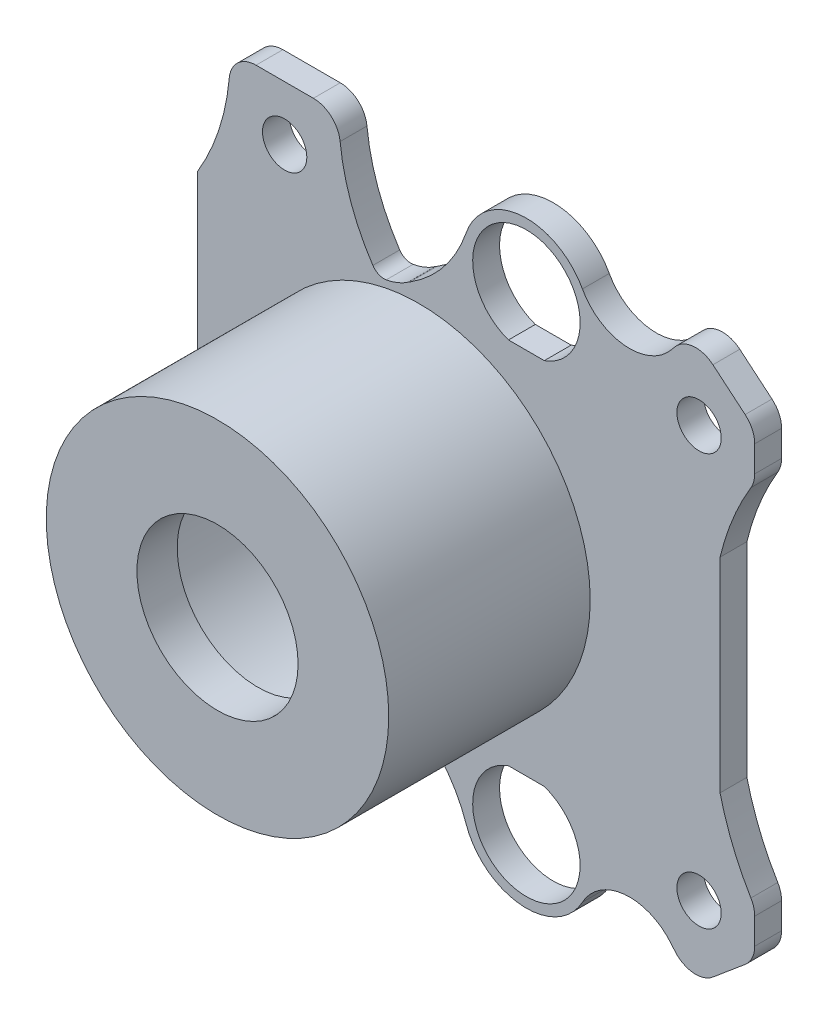
SolidWorks part; units mm, degrees
material "PETG"
ref_plane "Спереди" through (0, 0, 0) normal (0, 0, 1) x (1, 0, 0)
ref_plane "Сверху" through (0, 0, 0) normal (0, 1, 0) x (1, 0, 0)
ref_plane "Справа" through (0, 0, 0) normal (1, 0, 0) x (0, 0, -1)
sketch "Эскиз1" plane through (0, 0, 0) normal (0, 0, 1) x (1, 0, 0)
  line L0 (25, -14.2588) -> (25, -16.1977) construction
  line L1 (21.8887, -19.7411) -> (24.2856, -17.7298) construction
  line L2 (18.7497, -19.1116) -> (19.071, -19.4946) construction
  line L3 (-12.13, -22.05) -> (-7.8593, -22.05) construction
  line L4 (25, 16.1977) -> (25, 14.2588) construction
  line L5 (24.2856, 17.7298) -> (21.8887, 19.7411) construction
  line L6 (19.071, 19.4946) -> (18.7497, 19.1116) construction
  line L7 (-7.8593, 22.05) -> (-12.13, 22.05) construction
  line L8 (25, -14.2588) -> (25, -16.1977)
  line L9 (21.8887, -19.7411) -> (24.2856, -17.7298)
  line L10 (18.7497, -19.1116) -> (19.071, -19.4946)
  line L11 (-12.13, -22.05) -> (-7.8593, -22.05)
  line L12 (25, 16.1977) -> (25, 14.2588)
  line L13 (24.2856, 17.7298) -> (21.8887, 19.7411)
  line L14 (19.071, 19.4946) -> (18.7497, 19.1116)
  line L15 (-7.8593, 22.05) -> (-12.13, 22.05)
  line L16 (-16.5, -13) -> (-16.5, 13) construction
  line L17 (-16.5, -13) -> (-16.5, 13)
  line L18 (-3.4328, 13.4865) -> (-3.4328, 8.5896)
  line L19 (-3.4328, -13.4865) -> (-3.4328, -8.5896)
  line L20 (12, -17.5) -> (12, -13.7292) construction
  line L21 (20.1132, -7.6) -> (22.4198, -7.6) construction
  line L22 (22.4198, 7.6) -> (20.1132, 7.6) construction
  line L23 (12, 13.7292) -> (12, 17.5) construction
  line L24 (12, -17.5) -> (12, -13.7292)
  line L25 (20.1132, -7.6) -> (22.4198, -7.6)
  line L26 (22.4198, 7.6) -> (20.1132, 7.6)
  line L27 (12, 13.7292) -> (12, 17.5)
  line L30 (12, 17.5) -> (13.0411, 18.6816)
  line L31 (12, -17.5) -> (13.0411, -18.6816)
  circle A0 centre (20.8558, -15.3209) radius 2.05 construction
  circle A1 centre (-10, -18) radius 2.05 construction
  circle A2 centre (20.8558, 15.3209) radius 2.05 construction
  circle A3 centre (-10, 18) radius 2.05 construction
  circle A4 centre (20.8558, -15.3209) radius 2.05
  circle A5 centre (-10, -18) radius 2.05
  circle A6 centre (20.8558, 15.3209) radius 2.05
  circle A7 centre (-10, 18) radius 2.05
  arc A8 (22.4198, -7.6) -> (24.7157, -13.2309) centre (41.8722, -2.9522) ccw construction
  arc A9 (25, -14.2588) -> (24.7157, -13.2309) centre (23, -14.2588) ccw construction
  arc A10 (24.2856, -17.7298) -> (25, -16.1977) centre (23, -16.1977) ccw construction
  arc A11 (19.071, -19.4946) -> (21.8887, -19.7411) centre (20.6031, -18.209) ccw construction
  arc A12 (18.7497, -19.1116) -> (12.1721, -19.7707) centre (15.6855, -21.6828) ccw construction
  arc A13 (-3.4328, -13.4865) -> (-5.87, -20.2563) centre (9.05, -21.8039) ccw construction
  arc A14 (-7.8593, -22.05) -> (-5.87, -20.2563) centre (-7.8593, -20.05) ccw construction
  arc A15 (-14.1216, -20.2334) -> (-12.13, -22.05) centre (-12.13, -20.05) ccw construction
  arc A16 (-14.1216, -20.2334) -> (-16.5, -13) centre (-31.05, -21.7919) ccw construction
  arc A17 (24.7157, 13.2309) -> (22.4198, 7.6) centre (41.8722, 2.9522) ccw construction
  arc A18 (24.7157, 13.2309) -> (25, 14.2588) centre (23, 14.2588) ccw construction
  arc A19 (25, 16.1977) -> (24.2856, 17.7298) centre (23, 16.1977) ccw construction
  arc A20 (21.8887, 19.7411) -> (19.071, 19.4946) centre (20.6031, 18.209) ccw construction
  arc A21 (12.1721, 19.7707) -> (18.7497, 19.1116) centre (15.6855, 21.6828) ccw construction
  arc A22 (-5.87, 20.2563) -> (-3.4328, 13.4865) centre (9.05, 21.8039) ccw construction
  arc A23 (-5.87, 20.2563) -> (-7.8593, 22.05) centre (-7.8593, 20.05) ccw construction
  arc A24 (-16.5, 13) -> (-14.1216, 20.2334) centre (-31.05, 21.7919) ccw construction
  arc A25 (-12.13, 22.05) -> (-14.1216, 20.2334) centre (-12.13, 20.05) ccw construction
  arc A26 (22.4198, -7.6) -> (24.7157, -13.2309) centre (41.8722, -2.9522) ccw
  arc A27 (25, -14.2588) -> (24.7157, -13.2309) centre (23, -14.2588) ccw
  arc A28 (24.2856, -17.7298) -> (25, -16.1977) centre (23, -16.1977) ccw
  arc A29 (19.071, -19.4946) -> (21.8887, -19.7411) centre (20.6031, -18.209) ccw
  arc A30 (18.7497, -19.1116) -> (13.0411, -18.6816) centre (15.6855, -21.6828) ccw
  arc A31 (-3.4328, -13.4865) -> (-5.87, -20.2563) centre (9.05, -21.8039) ccw
  arc A32 (-7.8593, -22.05) -> (-5.87, -20.2563) centre (-7.8593, -20.05) ccw
  arc A33 (-14.1216, -20.2334) -> (-12.13, -22.05) centre (-12.13, -20.05) ccw
  arc A34 (-14.1216, -20.2334) -> (-16.5, -13) centre (-31.05, -21.7919) ccw
  arc A35 (24.7157, 13.2309) -> (22.4198, 7.6) centre (41.8722, 2.9522) ccw
  arc A36 (24.7157, 13.2309) -> (25, 14.2588) centre (23, 14.2588) ccw
  arc A37 (25, 16.1977) -> (24.2856, 17.7298) centre (23, 16.1977) ccw
  arc A38 (21.8887, 19.7411) -> (19.071, 19.4946) centre (20.6031, 18.209) ccw
  arc A39 (13.0411, 18.6816) -> (18.7497, 19.1116) centre (15.6855, 21.6828) ccw
  arc A40 (-5.87, 20.2563) -> (-3.4328, 13.4865) centre (9.05, 21.8039) ccw
  arc A41 (-5.87, 20.2563) -> (-7.8593, 22.05) centre (-7.8593, 20.05) ccw
  arc A42 (-16.5, 13) -> (-14.1216, 20.2334) centre (-31.05, 21.7919) ccw
  arc A43 (-12.13, 22.05) -> (-14.1216, 20.2334) centre (-12.13, 20.05) ccw
  arc A44 (4, 13.7292) -> (4, -13.7292) centre (8, 0) ccw construction
  arc A45 (-3.4328, 8.5896) -> (-3.4328, -8.5896) centre (8, 0) ccw
  arc A47 (12, -13.7292) -> (20.1132, -7.6) centre (8, 0) ccw construction
  arc A48 (20.1132, 7.6) -> (12, 13.7292) centre (8, 0) ccw construction
  arc A51 (12, -13.7292) -> (20.1132, -7.6) centre (8, 0) ccw
  arc A52 (20.1132, 7.6) -> (12, 13.7292) centre (8, 0) ccw
extrude "Бобышка-Вытянуть1" add sketch "Эскиз1" along normal blind 2
ref_plane "Плоскость1" through (0, 0, 14) normal (0, 0, 1) x (1, 0, 0)
sketch "Эскиз2" plane through (0, 0, 14) normal (0, 0, 1) x (1, 0, 0)
  line L0 (-3.4328, -13.4865) -> (-3.4328, -8.5896) construction
  line L1 (-3.4328, 8.5896) -> (-3.4328, 13.4865) construction
  line L2 (-3.4328, -12.2792) -> (-3.4328, -9.1257)
  line L3 (-3.4328, 9.1257) -> (-3.4328, 12.2792)
  arc A1 (-3.4328, 9.1257) -> (-3.4328, -9.1257) centre (0, 0) ccw
  arc A2 (-3.4328, 12.2792) -> (-3.4328, -12.2792) centre (0, 0) ccw
  dimension "D1" = 3
  dimension "D2" = 19.5
extrude "Бобышка-Вытянуть2" add sketch "Эскиз2" against normal up to surface (12 mm away) up to face at (-7.95, -18, 2)
sketch "Эскиз3" plane through (0, 0, 2) normal (0, 0, 1) x (1, 0, 0)
  line L2 (-3.4328, 8.5896) -> (-3.4328, 9.1257)
  line L3 (-3.4328, -9.1257) -> (-3.4328, -8.5896)
  line L4 (-3.4328, 8.5896) -> (-3.4328, 9.1257)
  line L5 (-3.4328, -9.1257) -> (-3.4328, -8.5896)
  arc A2 (-3.4328, 9.1257) -> (-3.4328, -9.1257) centre (0, 0) ccw
  arc A3 (-3.4328, 8.5896) -> (-3.4328, -8.5896) centre (8, 0) ccw
  arc A4 (-3.4328, 9.1257) -> (-3.4328, -9.1257) centre (0, 0) ccw
  arc A5 (-3.4328, 8.5896) -> (-3.4328, -8.5896) centre (8, 0) ccw
  dimension "D1" = 0
extrude "Вырез-Вытянуть1" cut sketch "Эскиз3" against normal up to surface (2 mm away) up to face at (-9.2556, 0, 0)
sketch "Эскиз9" plane through (0, 0, 2) normal (0, 0, 1) x (1, 0, 0)
  line L0 (0, 0) -> (50000, 0) construction
  line L1 (2.8707, 14) -> (50002.8707, 14) construction
  line L2 (-3.4328, 9.1257) -> (-3.4328, 13.4865) construction
  line L3 (-3.4328, 9.1257) -> (-3.4328, 13.4865)
  line L4 (-0.7921, 13.7292) -> (12, 13.7292)
  line L5 (-3.4328, 9.1257) -> (19.0096, 9.1257)
  line L11 (-3.4328, -9.1257) -> (-3.4328, -13.4865)
  line L12 (-3.4328, -9.1257) -> (19.0096, -9.1257)
  line L13 (-0.7921, -13.7292) -> (12, -13.7292)
  arc A0 (20.1132, 7.6) -> (12, 13.7292) centre (8, 0) ccw construction
  arc A1 (19.0096, 9.1257) -> (12, 13.7292) centre (8, 0) ccw
  arc A5 (-2.4359, 13.0546) -> (-0.9085, 13.6502) centre (-3.0946, 17) ccw construction
  arc A6 (-3.4328, 13.4865) -> (-2.4359, 13.0546) centre (-2.6006, 14.041) ccw construction
  arc A7 (-2.4359, 13.0546) -> (-0.9085, 13.6502) centre (-3.0946, 17) ccw construction
  arc A8 (-2.4359, -13.0546) -> (-0.7921, -13.7292) centre (-3.0946, -17) cw
  arc A9 (-2.4359, 13.0546) -> (-0.7921, 13.7292) centre (-3.0946, 17) ccw
  arc A10 (-3.4328, 13.4865) -> (-2.4359, 13.0546) centre (-2.6006, 14.041) ccw
  arc A11 (-3.4328, -13.4865) -> (-2.4359, -13.0546) centre (-2.6006, -14.041) cw
  arc A12 (19.0096, -9.1257) -> (12, -13.7292) centre (8, 0) cw
  point P11 (-1.8895, 13.1858)
  point P20 (12, 13.8511)
  dimension "D1" = 14
sketch "Эскиз10" plane through (0, 0, 2) normal (0, 0, 1) x (1, 0, 0)
  line L0 (20.1132, 7.6) -> (20.1132, -7.6)
  line L1 (20.1132, -7.6) -> (22.4198, -7.6)
  line L2 (22.4198, -7.6) -> (22.4198, 7.6)
  line L3 (22.4198, 7.6) -> (20.1132, 7.6)
extrude "Бобышка-Вытянуть8" add sketch "Эскиз10" against normal up to surface (2 mm away) up to face at (19.9093, 15.4291, 0)
extrude "Бобышка-Вытянуть9" add sketch "Эскиз9" against normal up to surface (2 mm away) up to face at (19.9093, 0, 0)
sketch "Эскиз11" plane through (0, 0, 2) normal (0, 0, 1) x (1, 0, 0)
  line L0 (-3.4328, -9.1257) -> (19.0096, -9.1257) construction
  line L1 (20.1132, -7.6) -> (20.1132, 7.6) construction
  line L2 (19.0096, 9.1257) -> (-3.4328, 9.1257) construction
  line L3 (-3.4328, -9.1257) -> (19.0096, -9.1257)
  line L4 (20.1132, -7.6) -> (20.1132, 7.6)
  line L5 (19.0096, 9.1257) -> (-3.4328, 9.1257)
  circle A0 centre (0, 0) radius 6.5
  circle A1 centre (0, 0) radius 4.5 construction
  arc A2 (19.0096, -9.1257) -> (20.1132, -7.6) centre (8, 0) ccw construction
  arc A3 (20.1132, 7.6) -> (19.0096, 9.1257) centre (8, 0) ccw construction
  arc A4 (-3.4328, 9.1257) -> (-3.4328, -9.1257) centre (0, 0) ccw construction
  arc A5 (19.0096, -9.1257) -> (20.1132, -7.6) centre (8, 0) ccw
  arc A6 (20.1132, 7.6) -> (19.0096, 9.1257) centre (8, 0) ccw
  arc A7 (-3.4328, 9.1257) -> (-3.4328, -9.1257) centre (0, 0) ccw
  point P8 (0, 0)
  point P10 (0, 0)
  dimension "D1" = 2
extrude "Бобышка-Вытянуть10" add sketch "Эскиз11" against normal up to surface (2 mm away) up to face at (10.8522, 0, 0)
sketch "Эскиз12" plane through (0, 0, 2) normal (0, 0, 1) x (1, 0, 0)
  line L0 (4, 17.5) -> (4, 13.7292) construction
  line L1 (13.0411, 18.6816) -> (12, 17.5) construction
  line L2 (-0.7921, 13.7292) -> (12, 13.7292) construction
  line L4 (4, 17.5) -> (4, 13.7292)
  line L5 (13.0411, 18.6816) -> (12, 17.5)
  line L6 (-0.7864, 13.7292) -> (4, 13.7292)
  line L7 (0, 0) -> (-50000, 0) construction
  line L8 (13.0411, -18.6816) -> (12, -17.5)
  line L9 (4, -17.5) -> (4, -13.7292)
  line L10 (-0.7864, -13.7292) -> (4, -13.7292)
  arc A0 (12, 17.5) -> (4, 17.5) centre (8, 17.5) ccw construction
  arc A1 (12.1721, 19.7707) -> (18.7497, 19.1116) centre (15.6855, 21.6828) ccw construction
  arc A2 (12.1721, 19.7707) -> (3.5082, 19.0446) centre (8, 17.5) ccw construction
  arc A3 (-0.6448, 13.8187) -> (3.5082, 19.0446) centre (-5.9483, 22.2965) ccw construction
  arc A4 (12, 17.5) -> (4, 17.5) centre (8, 17.5) ccw
  arc A5 (12.1721, 19.7707) -> (13.0411, 18.6816) centre (15.6855, 21.6828) ccw
  arc A6 (12.1721, 19.7707) -> (3.5082, 19.0446) centre (8, 17.5) ccw
  arc A7 (-0.6448, 13.8187) -> (3.5082, 19.0446) centre (-5.9483, 22.2965) ccw
  arc A8 (-0.6448, 13.8187) -> (-0.9085, 13.6502) centre (8, 0) ccw construction
  arc A9 (-0.6448, 13.8187) -> (-0.7864, 13.7292) centre (8, 0) ccw
  arc A10 (-0.6448, -13.8187) -> (-0.7864, -13.7292) centre (8, 0) cw
  arc A11 (-0.6448, -13.8187) -> (3.5082, -19.0446) centre (-5.9483, -22.2965) cw
  arc A12 (12.1721, -19.7707) -> (3.5082, -19.0446) centre (8, -17.5) cw
  arc A13 (12.1721, -19.7707) -> (13.0411, -18.6816) centre (15.6855, -21.6828) cw
  arc A14 (12, -17.5) -> (4, -17.5) centre (8, -17.5) cw
extrude "Бобышка-Вытянуть11" add sketch "Эскиз12" against normal up to surface (2 mm away) up to face at (8.161, 0, 0)
sketch "Эскиз13" plane through (0, 0, 2) normal (0, 0, 1) x (1, 0, 0)
  line L0 (12, 17.5) -> (12, 13.7292) construction
  line L1 (12, 13.7292) -> (4, 13.7292) construction
  line L2 (4, 13.7292) -> (4, 17.5) construction
  line L3 (12, 17.5) -> (12, 13.7292)
  line L4 (12, 13.7292) -> (9.3345, 13.7292)
  line L5 (4, 13.7292) -> (4, 17.5)
  line L6 (6.6655, 13.7292) -> (4, 13.7292)
  line L7 (0, 0) -> (-50000, 0) construction
  line L8 (12, -13.7292) -> (9.3345, -13.7292)
  line L9 (12, -17.5) -> (12, -13.7292)
  line L10 (6.6655, -13.7292) -> (4, -13.7292)
  line L11 (4, -13.7292) -> (4, -17.5)
  arc A1 (4, 17.5) -> (6.6655, 13.7292) centre (8, 17.5) ccw
  arc A2 (12, 17.5) -> (4, 17.5) centre (8, 17.5) ccw construction
  arc A3 (9.3345, 13.7292) -> (12, 17.5) centre (8, 17.5) ccw
  arc A4 (9.3345, -13.7292) -> (12, -17.5) centre (8, -17.5) cw
  arc A5 (4, -17.5) -> (6.6655, -13.7292) centre (8, -17.5) cw
extrude "Бобышка-Вытянуть12" add sketch "Эскиз13" against normal up to surface (2 mm away) up to face at (6.6107, 0, 0)
sketch "Эскиз15" plane through (0, 0, 2) normal (0, 0, 1) x (1, 0, 0)
  line L0 (-3.4328, -12.2792) -> (-3.4328, -9.1257) construction
  line L1 (-3.4328, 12.2792) -> (-3.4328, 9.1257) construction
  line L2 (-3.4328, -12.2792) -> (-3.4328, -9.1257)
  line L3 (-3.4328, 12.2792) -> (-3.4328, 9.1257)
  arc A0 (-3.4328, -9.1257) -> (-3.4328, 9.1257) centre (0, 0) ccw
  arc A1 (-3.4328, 9.1257) -> (-3.4328, -9.1257) centre (0, 0) ccw construction
  arc A2 (-3.4328, -12.2792) -> (-3.4328, 12.2792) centre (0, 0) ccw
  arc A3 (-3.4328, 12.2792) -> (-3.4328, -12.2792) centre (0, 0) ccw construction
extrude "Бобышка-Вытянуть14" add sketch "Эскиз15" along normal up to surface (12 mm away) up to face at (-7.3414, 0, 14)
sketch "Эскиз16" plane through (0, 0, 2) normal (0, 0, 1) x (1, 0, 0)
  circle A1 centre (0, 0) radius 9.75
  circle A2 centre (0, 0) radius 9.75
  dimension "D1" = 0
extrude "Вырез-Вытянуть2" cut sketch "Эскиз16" against normal up to surface (2 mm away) up to face at (8, -17.6146, 0)
sketch "Эскиз17" plane through (0, 0, 14) normal (0, 0, 1) x (1, 0, 0)
  circle A0 centre (0, 0) radius 6
  circle A1 centre (0, 0) radius 12.75
  circle A2 centre (0, 0) radius 12.75
  dimension "D2" = 12
  dimension "D1" = 0
extrude "Бобышка-Вытянуть15" add sketch "Эскиз17" along normal blind 3
sketch "Эскиз18" plane through (0, 0, 2) normal (0, 0, 1) x (1, 0, 0)
  circle A0 centre (-10, -18) radius 2.05 construction
  circle A1 centre (20.8558, -15.3209) radius 2.05 construction
  circle A2 centre (20.8558, 15.3209) radius 2.05 construction
  circle A3 centre (-10, 18) radius 2.05 construction
  circle A4 centre (-10, -18) radius 2.05
  circle A5 centre (20.8558, -15.3209) radius 2.05
  circle A6 centre (20.8558, 15.3209) radius 2.05
  circle A7 centre (-10, 18) radius 2.05
  circle A8 centre (-10, 18) radius 1.65
  circle A9 centre (20.8558, 15.3209) radius 1.65
  circle A10 centre (20.8558, -15.3209) radius 1.65
  circle A11 centre (-10, -18) radius 1.65
  dimension "D1" = 3.3
extrude "Бобышка-Вытянуть16" add sketch "Эскиз18" against normal up to surface (2 mm away) up to face at (9.75, 0, 0)
